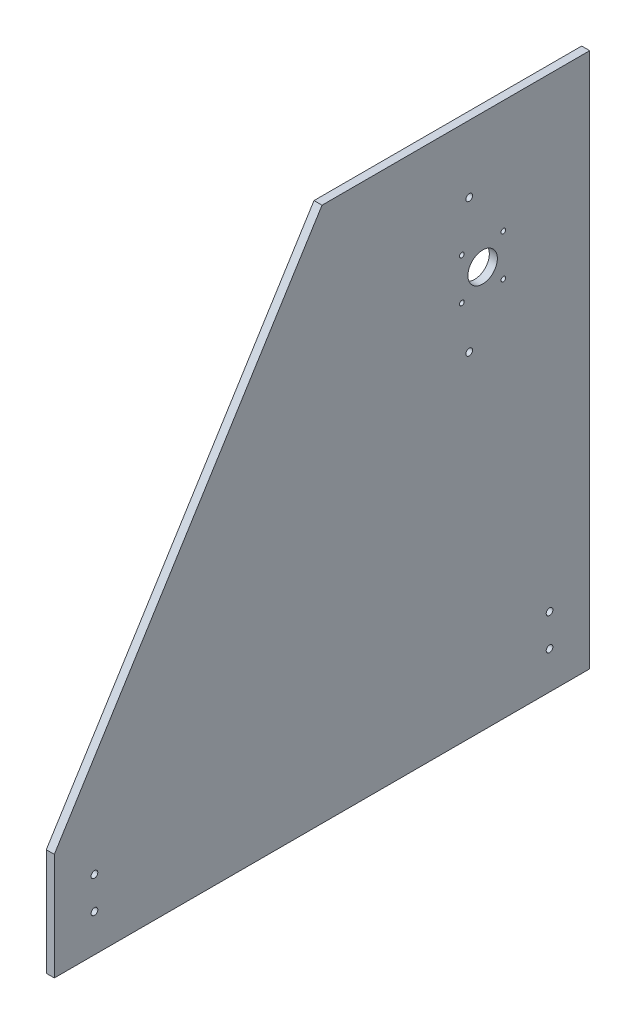
SolidWorks part; units mm, degrees
ref_plane "Front Plane" through (0, 0, 0) normal (0, 0, 1) x (1, 0, 0)
ref_plane "Top Plane" through (0, 0, 0) normal (0, 1, 0) x (1, 0, 0)
ref_plane "Right Plane" through (0, 0, 0) normal (1, 0, 0) x (0, 0, -1)
sketch "Sketch1" plane through (0, 0, 0) normal (1, 0, 0) x (0, 0, -1)
  line L0 (0, -2343.7616) -> (0, 114844.3172) construction
  line L1 (-2343.7616, 0) -> (114844.3172, 0) construction
  line L2 (0, 80) -> (400, 80) construction
  line L3 (0, 0) -> (400, 0)
  line L5 (200, 400) -> (400, 400)
  line L6 (400, 0) -> (400, 400)
  line L7 (0, 80) -> (200, 400)
  line L8 (0, 80) -> (0, 0)
  line L9 (-1000, 40) -> (49000, 40) construction
  line L10 (200, -1000) -> (200, 49000) construction
  line L11 (310, -1000) -> (310, 49000) construction
  line L12 (320, -1008.4066) -> (320, 48991.5934) construction
  line L13 (298.2689, 300) -> (341.7311, 300) construction
  circle A0 centre (30, 52) radius 2.5
  circle A2 centre (30, 28) radius 2.5
  circle A3 centre (370, 28) radius 2.5
  circle A4 centre (370, 52) radius 2.5
  circle A5 centre (310, 350) radius 2.5
  circle A6 centre (310, 250) radius 2.5
  circle A7 centre (320, 300) radius 11
  circle A8 centre (335.5, 315.5) radius 1.75
  circle A9 centre (304.5, 315.5) radius 1.75
  circle A10 centre (304.5, 284.5) radius 1.75
  circle A11 centre (335.5, 284.5) radius 1.75
  point P14 (0, 40)
  point P21 (200, 0)
  point P38 (320, 300)
  dimension "D7" = 5
  dimension "D9" = 5
  dimension "D14" = 22
  dimension "D16" = 15.5
  dimension "D17" = 3.5
  dimension "D1" = 400
  dimension "D2" = 400
  dimension "D3" = 80
  dimension "D4" = 200
  dimension "D5" = 30
  dimension "D6" = 90
  dimension "D8" = 12
  dimension "D10" = 50
  dimension "D11" = 100
  dimension "D12" = 80
  dimension "D13" = 50
  dimension "D15" = 15.5
extrude "Boss-Extrude1" add sketch "Sketch1" along normal blind 6
